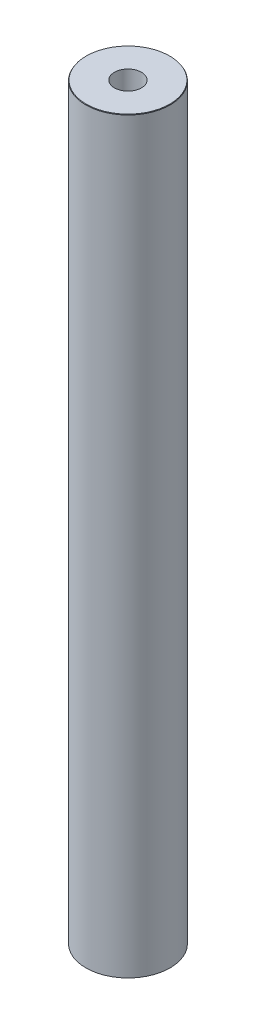
SolidWorks part; units mm, degrees
ref_plane "Front Plane" through (0, 0, 0) normal (0, 0, 1) x (1, 0, 0)
ref_plane "Top Plane" through (0, 0, 0) normal (0, 1, 0) x (1, 0, 0)
ref_plane "Right Plane" through (0, 0, 0) normal (1, 0, 0) x (0, 0, -1)
sketch "Sketch1" plane through (0, 0, 0) normal (0, 1, 0) x (1, 0, 0)
  circle A0 centre (0, 0) radius 32.5
  dimension "SHAFT_OD" = 65
extrude "Boss-Extrude1" add sketch "Sketch1" along normal blind 578.1175
sketch "Sketch2" plane through (0, 0, 0) normal (0, 1, 0) x (1, 0, 0)
  circle A0 centre (0, 0) radius 10.469
  dimension "BORE_D" = 20.938
extrude "Cut-Extrude1" cut sketch "Sketch2" along normal through all
chamfer "Chamfer1" distance 0.4454 angle 30 2 edges at (0, 578.1175, 32.5) (0, 0, 32.5) first distance on face at (0, 578.1175, 32.5) first distance on face at (0, 0, 10.469)
